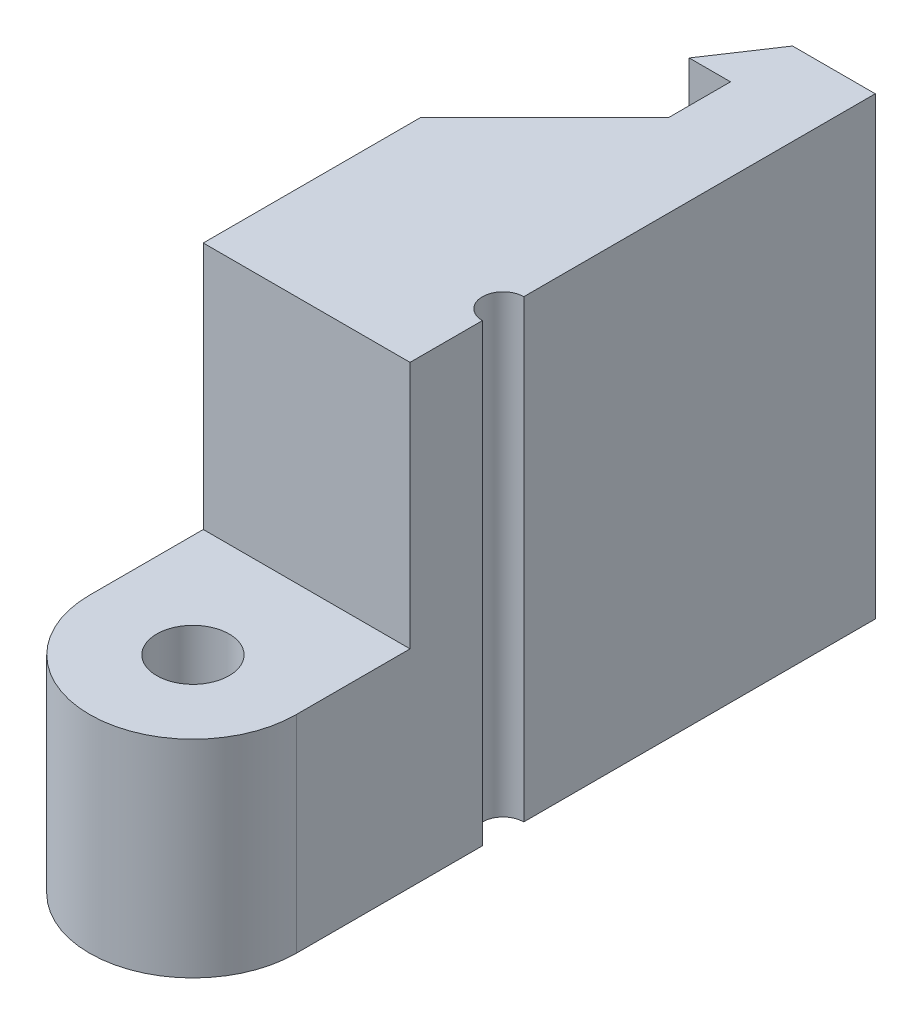
SolidWorks part; units mm, degrees
ref_plane "Front Plane" through (0, 0, 0) normal (0, 0, 1) x (1, 0, 0)
ref_plane "Top Plane" through (0, 0, 0) normal (0, 1, 0) x (1, 0, 0)
ref_plane "Right Plane" through (0, 0, 0) normal (1, 0, 0) x (0, 0, -1)
sketch "Sketch1" plane through (0, 0, 0) normal (0, 1, 0) x (1, 0, 0)
  line L0 (0, 0) -> (0, 43.6303) construction
  line L1 (-5, 0) -> (-5, 43.6303)
  line L2 (5, 0) -> (5, 9)
  line L3 (5, 11) -> (5, 43.6303)
  line L4 (-5, 20) -> (5, 20) construction
  line L5 (-5, 22) -> (5, 22)
  arc A0 (-5, 0) -> (5, 0) centre (0, 0) ccw
  arc A1 (5, 43.6303) -> (-5, 43.6303) centre (0, 43.6303) ccw
  circle A2 centre (0, 0) radius 1.75
  arc A3 (5, 11) -> (5, 9) centre (5, 10) ccw
  circle A4 centre (5, 10) radius 39 construction
  circle A5 centre (0, 15) radius 1.75 construction
  dimension "D1" = 3.5
  dimension "D2" = 2
  dimension "D4" = 5
  dimension "D6" = 78
  dimension "D8" = 3.5
  dimension "D10" = 7
  dimension "D3" = 0
  dimension "D5" = 10
  dimension "D7" = 10
  dimension "D9" = 5
extrude "Boss-Extrude1" add sketch "Sketch1" along normal blind 10 contours A3 L3 L5 L1 A0 L2 A2 region at (-0.029, 0, -9.3558)
sketch "Sketch2" plane through (5, 0, 0) normal (1, 0, 0) x (0, 0, -1)
  line L0 (10, 0) -> (10, 10) construction
  line L1 (10, 5) -> (20, 5)
  line L4 (9, 0) -> (11, 0)
  line L5 (11, 0) -> (11, 10)
  line L6 (9, 0) -> (11, 0)
  line L7 (9, 10) -> (9, 0)
  line L9 (11, 0) -> (11, 10) construction
  line L11 (9, 10) -> (9, 0) construction
  line L14 (11, 10) -> (9, 10)
  line L15 (11, 10) -> (9, 10)
  circle A0 centre (20, 5) radius 2.5
  dimension "D2" = 5
  dimension "D3" = 10
  dimension "D1" = 0
extrude "Cut-Extrude1" [suppressed] cut sketch "Sketch2" against normal through all contours A0
sketch "Sketch3" plane through (0, 10, 0) normal (0, 1, 0) x (1, 0, 0)
  line L0 (-5, 0) -> (-5, 22) construction
  line L1 (5, 5.5) -> (-5, 5.5)
  line L2 (5, 5.5) -> (5, 9)
  line L3 (5, 22) -> (-5, 22)
  line L4 (-5, 5.5) -> (-5, 22)
  line L5 (5, 11) -> (5, 22)
  line L6 (-5, 22) -> (5, 22) construction
  line L8 (5, 11) -> (5, 22) construction
  circle A0 centre (0, 0) radius 5.5 construction
  arc A2 (5, 11) -> (5, 9) centre (5, 10) ccw
  arc A3 (5, 11) -> (5, 9) centre (5, 10) ccw construction
  point P9 (-5, 22)
  dimension "D1" = 11
extrude "Boss-Extrude2" add sketch "Sketch3" along normal blind 12
ref_plane "Plane1" through (0, 0, -55) normal (0, 0, 1) x (1, 0, 0)
sketch "Sketch4" plane through (0, 0, -55) normal (0, 0, 1) x (1, 0, 0)
  line L0 (0, 0) -> (0, 5) construction
  line L1 (0, 5) -> (-5, 5) construction
  line L2 (-5, 10) -> (-5, 0) construction
  line L3 (-5, 5) -> (0, 5)
  circle A0 centre (0, 5) radius 2
  dimension "D1" = 4
extrude "Cut-Extrude2" [suppressed] cut sketch "Sketch4" along normal blind 25 contours A0
sketch "Sketch5" plane through (0, 22, 0) normal (0, 1, 0) x (1, 0, 0)
  line L0 (5, 22) -> (5, 28)
  line L1 (5, 28) -> (1, 28)
  line L2 (1, 28) -> (-1, 25)
  line L3 (-1, 25) -> (1, 25)
  line L4 (1, 25) -> (1, 22)
  line L5 (5, 22) -> (-5, 22) construction
  line L6 (1, 22) -> (5, 22)
  dimension "D1" = 3
  dimension "D2" = 4
  dimension "D3" = 3
  dimension "D4" = 2
extrude "Boss-Extrude3" add sketch "Sketch5" against normal up to surface (22 mm away) up to face at (1.5, 0, -9.8333)
chamfer "Chamfer1" distance 6 angle 45 1 edges at (-5, 11, -22)
